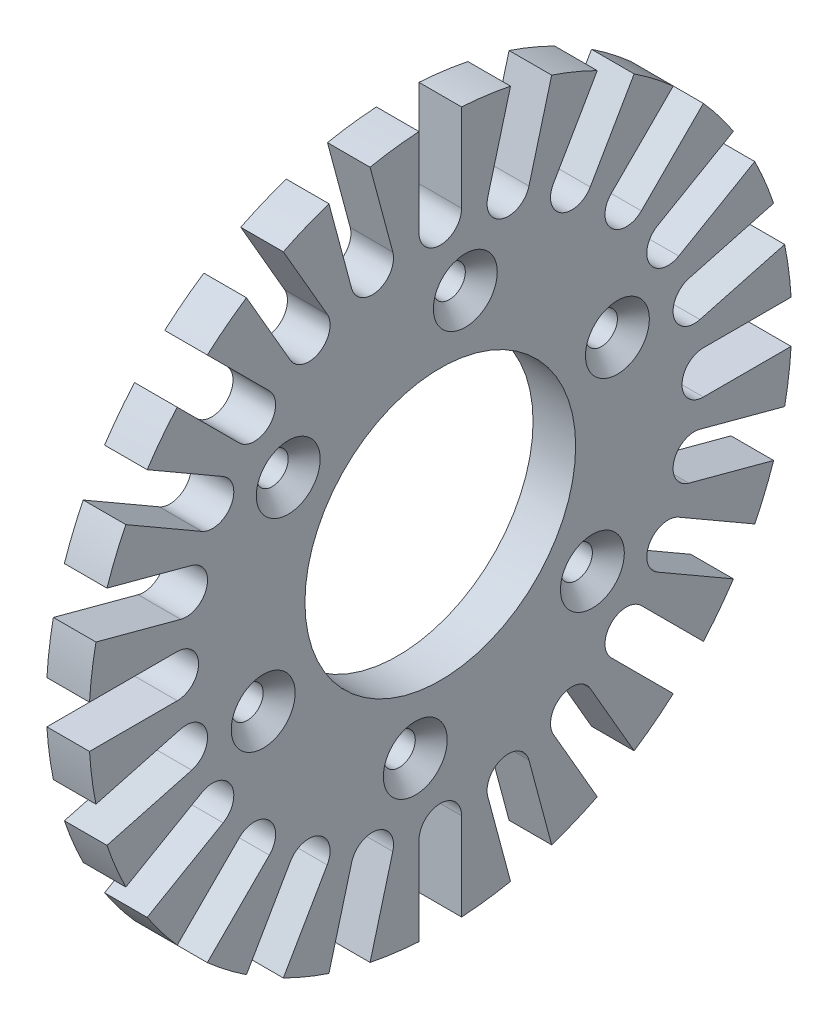
SolidWorks part; units mm, degrees
material "1060 Alloy"
ref_plane "Front Plane" through (0, 0, 0) normal (0, 0, 1) x (1, 0, 0)
ref_plane "Top Plane" through (0, 0, 0) normal (0, 1, 0) x (1, 0, 0)
ref_plane "Right Plane" through (0, 0, 0) normal (1, 0, 0) x (0, 0, -1)
sketch "Sketch1" plane through (0, 0, 0) normal (1, 0, 0) x (0, 0, -1)
  circle A0 centre (0, 0) radius 33
  dimension "D1" = 66
extrude "Boss-Extrude1" add sketch "Sketch1" along normal blind 4
sketch "Sketch3" plane through (4, 0, 0) normal (1, 0, 0) x (0, 0, -1)
  circle A0 centre (0, 0) radius 12.71
  dimension "D1" = 25.42
extrude "Cut-Extrude2" cut sketch "Sketch3" against normal up to next
sketch "Sketch4" plane through (4, 0, 0) normal (1, 0, 0) x (0, 0, -1)
  line L0 (-2, 33) -> (-2, 24.7)
  line L1 (2, 24.7) -> (2, 33)
  line L2 (2, 33) -> (-2, 33)
  arc A0 (-2, 24.7) -> (2, 24.7) centre (0, 24.7) ccw
  circle A1 centre (0, 0) radius 33 construction
  dimension "D1" = 4
  dimension "D2" = 8.3
extrude "Cut-Extrude3" cut sketch "Sketch4" against normal up to next
pattern_circular "CirPattern2" count 24 over 360 about axis through (4, 0, 0) along (1, 0, 0) of "Cut-Extrude3"
sketch "Sketch2" plane through (4, 0, 0) normal (1, 0, 0) x (0, 0, -1)
  line L0 (2.3495, 17.846) -> (0, 0) construction
  line L1 (0, 0) -> (12.71, 0) construction
  circle A0 centre (2.3495, 17.846) radius 1.5
  circle A1 centre (0, 0) radius 12.71 construction
  dimension "D1" = 3
  dimension "D2" = 18
  dimension "D3" = 82.5
extrude "Cut-Extrude1" cut sketch "Sketch2" against normal up to next
chamfer "Chamfer1" distance 1.5 angle 45 1 edges at (4, 17.846, -3.8495)
pattern_circular "CirPattern1" count 6 over 360 about axis through (4, 0, 0) along (1, 0, 0) of "Cut-Extrude1", "Chamfer1"
